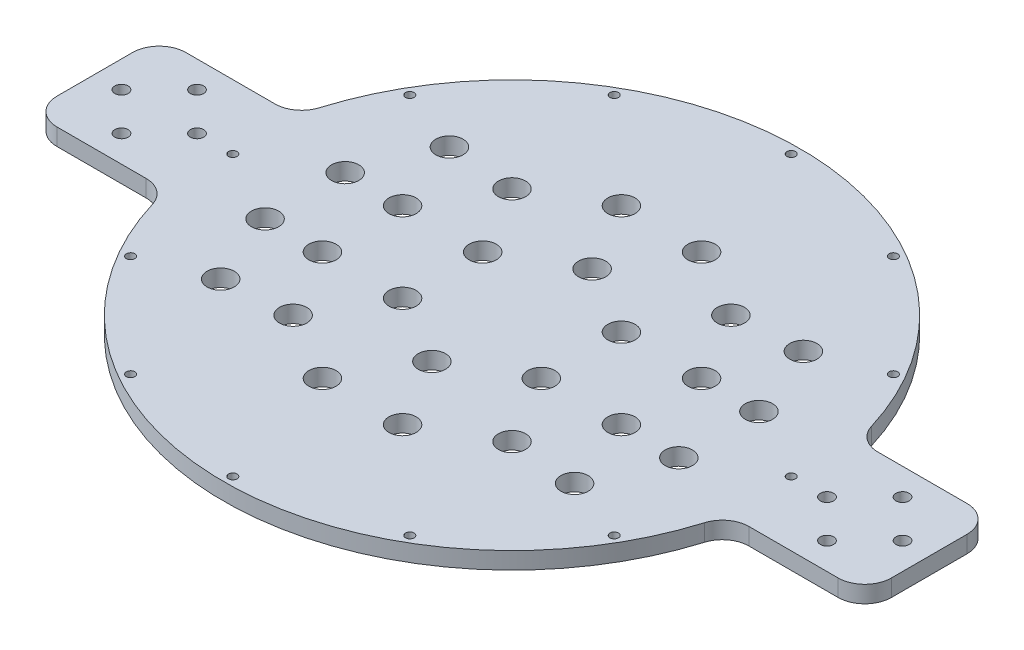
SolidWorks part; units mm, degrees
material "AISI 304"
ref_plane "Front Plane" through (0, 0, 0) normal (0, 0, 1) x (1, 0, 0)
ref_plane "Top Plane" through (0, 0, 0) normal (0, 1, 0) x (1, 0, 0)
ref_plane "Right Plane" through (0, 0, 0) normal (1, 0, 0) x (0, 0, -1)
sketch "Sketch1" plane through (0, 0, 0) normal (0, 1, 0) x (1, 0, 0)
  circle A1 centre (0, 0) radius 107.95
  dimension "D2" = 215.9
extrude "Boss-Extrude1" add sketch "Sketch1" along normal blind 6.35
hole_wizard "M3 Clearance Hole1" positions "Sketch9" profile "Sketch10" hole size "M3" standard "ANSI Metric" end condition through all
sketch "Sketch9" plane through (0, 6.35, 0) normal (0, 1, 0) x (1, 0, 0)
  line L0 (0, 0) -> (0, 104.55) construction
  point P2 (0, 104.55)
  dimension "D1" = 104.55
sketch "Sketch10" plane through (0, 6.35, -104.55) normal (1, 0, 0) x (0, 0, 1)
  line L0 (0, 0) -> (0, 6.35)
  line L1 (0, 6.35) -> (1.6, 6.35)
  line L2 (1.6, 6.35) -> (1.6, 0)
  line L5 (1.6, 0) -> (0, 0)
  line L11 (0, -6.35) -> (0, 107.95) construction
  dimension "Thru Hole Dia." = 3.2
  dimension "Thru Hole Depth" = 6.35
pattern_circular "CirPattern1" count 12 over 360 about axis through (0, 6.35, 0) along (0, -1, 0) of "M3 Clearance Hole1" reverse direction yes
sketch "Sketch2" plane through (0, 0, 0) normal (0, 1, 0) x (1, 0, 0)
  line L0 (-156.2343, 24.1421) -> (-105.2158, 24.1421)
  line L1 (-105.2158, -24.1421) -> (-156.2343, -24.1421)
  line L2 (-156.2343, -24.1421) -> (-156.2343, 24.1421)
  line L3 (-156.2343, 0) -> (0, 0) construction
  line L4 (-146.2343, 0) -> (-132.0921, 14.1421) construction
  line L5 (-132.0921, 14.1421) -> (-117.95, 0) construction
  line L6 (-117.95, 0) -> (-132.0921, -14.1421) construction
  line L7 (-132.0921, -14.1421) -> (-146.2343, 0) construction
  circle A0 centre (0, 0) radius 107.95 construction
  circle A1 centre (0, 0) radius 107.95 construction
  arc A2 (-105.2158, 24.1421) -> (-105.2158, -24.1421) centre (0, 0) ccw
  point P11 (-107.95, 0)
  dimension "D1" = 20
  dimension "D2" = 10
  dimension "D3" = 10
  dimension "D4" = 10
extrude "Boss-Extrude2" add sketch "Sketch2" along normal up to surface (6.35 mm away) up to face at (52.275, 6.35, -88.943)
fillet "Fillet1" radius 10 4 edges at (-105.2158, 3.175, -24.1421) (-156.2343, 3.175, -24.1421) (-156.2343, 3.175, 24.1421) (-105.2158, 3.175, 24.1421)
mirror "Mirror1" about plane through (0, 0, 0) normal (1, 0, 0) of "Boss-Extrude2", "Fillet1"
hole_wizard "#10 Clearance Hole3" positions "Sketch7" profile "Sketch8" hole size "#10" standard "ANSI Inch" end condition through all
sketch "Sketch7" plane through (0, 6.35, 0) normal (0, 1, 0) x (1, 0, 0)
  line L0 (-117.95, 0) -> (-132.0921, -14.1421) construction
  line L1 (-132.0921, -14.1421) -> (-146.2343, 0) construction
  line L2 (-146.2343, 0) -> (-132.0921, 14.1421) construction
  line L3 (-132.0921, 14.1421) -> (-117.95, 0) construction
  line L4 (-117.95, 0) -> (-132.0921, -14.1421) construction
  line L5 (-132.0921, -14.1421) -> (-146.2343, 0) construction
  line L6 (-146.2343, 0) -> (-132.0921, 14.1421) construction
  line L7 (-132.0921, 14.1421) -> (-117.95, 0) construction
  line L8 (0, 107.95) -> (0, -107.95) construction
  line L10 (132.0921, 14.1421) -> (117.95, 0) construction
  line L11 (146.2343, 0) -> (132.0921, 14.1421) construction
  line L12 (132.0921, -14.1421) -> (146.2343, 0) construction
  line L13 (117.95, 0) -> (132.0921, -14.1421) construction
  arc A0 (103.3286, 31.2475) -> (-103.3286, 31.2475) centre (0, 0) ccw construction
  arc A1 (-103.3286, -31.2475) -> (103.3286, -31.2475) centre (0, 0) ccw construction
  point P0 (-132.0921, -14.1421)
  point P2 (-117.95, 0)
  point P4 (-132.0921, 14.1421)
  point P6 (-146.2343, 0)
  point P29 (146.2343, 0)
  point P30 (132.0921, 14.1421)
  point P31 (117.95, 0)
  point P32 (132.0921, -14.1421)
sketch "Sketch8" plane through (-132.0921, 6.35, 14.1421) normal (1, 0, 0) x (0, 0, 1)
  line L0 (0, 0) -> (0, 6.35)
  line L1 (0, 6.35) -> (2.4892, 6.35)
  line L2 (2.4892, 6.35) -> (2.4892, 0)
  line L5 (2.4892, 0) -> (0, 0)
  line L11 (0, -6.35) -> (0, 107.95) construction
  dimension "Thru Hole Dia." = 4.9784
  dimension "Thru Hole Depth" = 6.35
sketch "Sketch11" plane through (0, 6.35, 0) normal (0, 1, 0) x (1, 0, 0)
  line L0 (-88.9, 0) -> (0, 0) construction
  line L1 (0, 0) -> (0, 88.9) construction
  circle A0 centre (0, 0) radius 88.9 construction
  circle A1 centre (-66.2622, 42.8314) radius 5.1
  circle A2 centre (-77.461, 15) radius 5.1
  circle A3 centre (-77.461, -15) radius 5.1
  circle A4 centre (-66.2622, -42.8314) radius 5.1
  circle A9 centre (0, 30) radius 5.1
  circle A10 centre (-25.9808, 15) radius 5.1
  circle A11 centre (25.9808, 15) radius 5.1
  circle A12 centre (-25.9808, -15) radius 5.1
  circle A13 centre (25.9808, -15) radius 5.1
  circle A14 centre (-55.9808, -15) radius 5.1
  circle A15 centre (-40.9808, -40.9808) radius 5.1
  circle A16 centre (-15, -55.9808) radius 5.1
  circle A17 centre (15, -55.9808) radius 5.1
  circle A18 centre (-55.9808, 15) radius 5.1
  circle A20 centre (55.9808, -15) radius 5.1
  circle A21 centre (40.9808, -40.9808) radius 5.1
  circle A26 centre (0, 0) radius 30 construction
  arc A27 (-64.809, 45) -> (-64.809, -45) centre (0, 0) ccw construction
  circle A28 centre (66.2622, -42.8314) radius 5.1
  circle A29 centre (77.461, -15) radius 5.1
  circle A30 centre (77.461, 15) radius 5.1
  circle A31 centre (66.2622, 42.8314) radius 5.1
  circle A32 centre (0, 0) radius 57.9555 construction
  circle A33 centre (55.9808, 15) radius 5.1
  circle A34 centre (40.9808, 40.9808) radius 5.1
  circle A35 centre (15, 55.9808) radius 5.1
  circle A36 centre (-15, 55.9808) radius 5.1
  circle A37 centre (-40.9808, 40.9808) radius 5.1
  circle A38 centre (0, -30) radius 5.1
  dimension "D1" = 177.8
  dimension "D2" = 10.2
  dimension "D3" = 30
  dimension "D8" = 10
  dimension "D9" = 90
  dimension "D11" = 30
  dimension "D4" = 30
  dimension "D5" = 30
  dimension "D6" = 30
  dimension "D7" = 30
  dimension "D10" = 30
  dimension "D12" = 30
  dimension "D13" = 30
  dimension "D14" = 30
  dimension "D15" = 30
  dimension "D16" = 30
  dimension "D17" = 30
  dimension "D18" = 30
  dimension "D19" = 30
  dimension "D20" = 30
extrude "Cut-Extrude1" cut sketch "Sketch11" against normal up to next (6.35 mm away)
